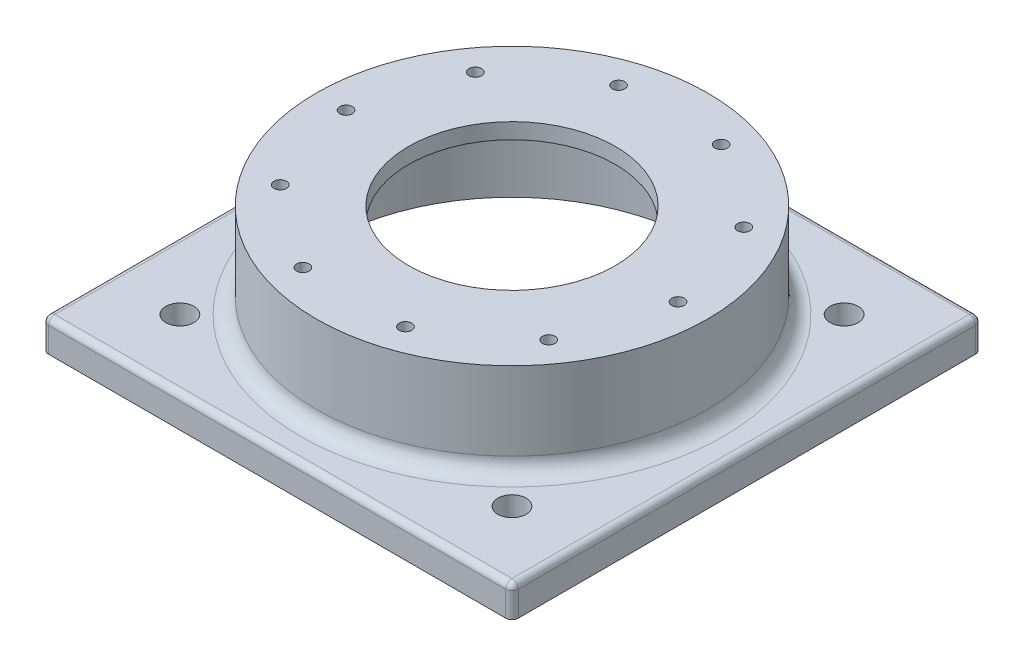
SolidWorks part; units mm, degrees
ref_plane "Спереди" through (0, 0, 0) normal (0, 0, 1) x (1, 0, 0)
ref_plane "Сверху" through (0, 0, 0) normal (0, 1, 0) x (1, 0, 0)
ref_plane "Справа" through (0, 0, 0) normal (1, 0, 0) x (0, 0, -1)
sketch "Эскиз1" plane through (0, 0, 0) normal (0, 1, 0) x (1, 0, 0)
  line L0 (0, 0) -> (53.033, 53.033) construction
  line L5 (75, -75) -> (-75, -75)
  line L6 (75, -75) -> (75, 75)
  line L7 (75, 75) -> (-75, 75)
  line L8 (-75, -75) -> (-75, 75)
  line L9 (75, -75) -> (-75, 75) construction
  line L10 (75, 75) -> (-75, -75) construction
  circle A2 centre (0, 0) radius 75 construction
  circle A3 centre (53.033, 53.033) radius 4.5
  circle A4 centre (0, 0) radius 75 construction
  circle A5 centre (53.033, -53.033) radius 4.5
  circle A6 centre (0, 0) radius 75 construction
  circle A7 centre (-53.033, -53.033) radius 4.5
  circle A8 centre (0, 0) radius 75 construction
  circle A9 centre (-53.033, 53.033) radius 4.5
  point P0 (0, 0)
  dimension "D3" = 150
  dimension "D4" = 9
  dimension "D1" = 150
  dimension "D2" = 150
  dimension "D5" = 4
extrude "Бобышка-Вытянуть1" add sketch "Эскиз1" along normal blind 10
fillet "Скругление1" radius 2 4 edges at (-75, 5, -75) (75, 5, -75) (-75, 5, 75) (75, 5, 75)
fillet "Скругление2" radius 2 8 edges at (-74.4142, 10, -74.4142) (74.4142, 10, -74.4142) (74.4142, 10, 74.4142) (-74.4142, 10, 74.4142) (0, 10, 75) (75, 10, 0) (0, 10, -75) (-75, 10, 0)
sketch "Эскиз4" plane through (0, 10, 0) normal (0, 1, 0) x (1, 0, 0)
  circle A0 centre (0, 0) radius 62.5
  dimension "D1" = 125
extrude "Бобышка-Вытянуть4" add sketch "Эскиз4" along normal blind 30 contours A0
fillet "Скругление5" radius 5 1 edges at (0, 10, 62.5)
sketch "Эскиз10" plane through (0, 0, 0) normal (0, -1, 0) x (1, 0, 0)
  circle A0 centre (0, 0) radius 60
  dimension "D1" = 120
sketch "Эскиз3" plane through (0, 10, 0) normal (0, 1, 0) x (1, 0, 0)
  line L0 (0, -75) -> (0, 75)
  line L1 (-73, 75) -> (73, 75) construction
  circle A1 centre (-53.033, 53.033) radius 6.25
  circle A2 centre (-53.033, -53.033) radius 6.25
  circle A3 centre (53.033, -53.033) radius 6.25
  circle A4 centre (53.033, 53.033) radius 6.25
  point P14 (0, 0)
  dimension "D2" = 12.5
  dimension "D3" = 12.5
  dimension "D1" = 150
extrude "Вырез-Вытянуть1" [suppressed] cut sketch "Эскиз3" along normal up to next contours A3 | A2 | A1 | A4
sketch "Эскиз11" plane through (0, 40, 0) normal (0, 1, 0) x (1, 0, 0)
  circle A0 centre (0, 0) radius 33
  dimension "D1" = 66
extrude "Вырез-Вытянуть2" cut sketch "Эскиз11" against normal through all contours A0
extrude "Вырез-Вытянуть3" cut sketch "Эскиз10" against normal blind 35 contours A0
sketch "Эскиз12" plane through (0, 40, 0) normal (0, 1, 0) x (1, 0, 0)
  line L0 (0, 0) -> (-53, 0) construction
  circle A0 centre (0, 0) radius 53 construction
  circle A1 centre (-53, 0) radius 2
  circle A2 centre (0, 0) radius 53
  circle A3 centre (0, 0) radius 33 construction
  circle A4 centre (-42.8779, 31.1526) radius 2
  circle A5 centre (0, 0) radius 53
  circle A6 centre (-16.3779, 50.406) radius 2
  circle A7 centre (0, 0) radius 53
  circle A8 centre (16.3779, 50.406) radius 2
  circle A9 centre (0, 0) radius 53
  circle A10 centre (42.8779, 31.1526) radius 2
  circle A11 centre (0, 0) radius 53
  circle A12 centre (53, 0) radius 2
  circle A13 centre (0, 0) radius 53
  circle A14 centre (42.8779, -31.1526) radius 2
  circle A15 centre (0, 0) radius 53
  circle A16 centre (16.3779, -50.406) radius 2
  circle A17 centre (0, 0) radius 53
  circle A18 centre (-16.3779, -50.406) radius 2
  circle A19 centre (0, 0) radius 53
  circle A20 centre (-42.8779, -31.1526) radius 2
  dimension "D2" = 4
  dimension "D3" = 53
  dimension "D5" = 53
  dimension "D4" = 10
extrude "Вырез-Вытянуть4" cut sketch "Эскиз12" against normal through all contours A4 | A1 | A20 | A18 | A16 | A14 | A12 | A10 | A8 | A6
equation "\"D2@Эскиз1\"=\"D1@Эскиз1\""
equation "\"D3@Эскиз1\"=\"D1@Эскиз1\""
equation "\"D3@Эскиз3\"=\"D2@Эскиз3\""
